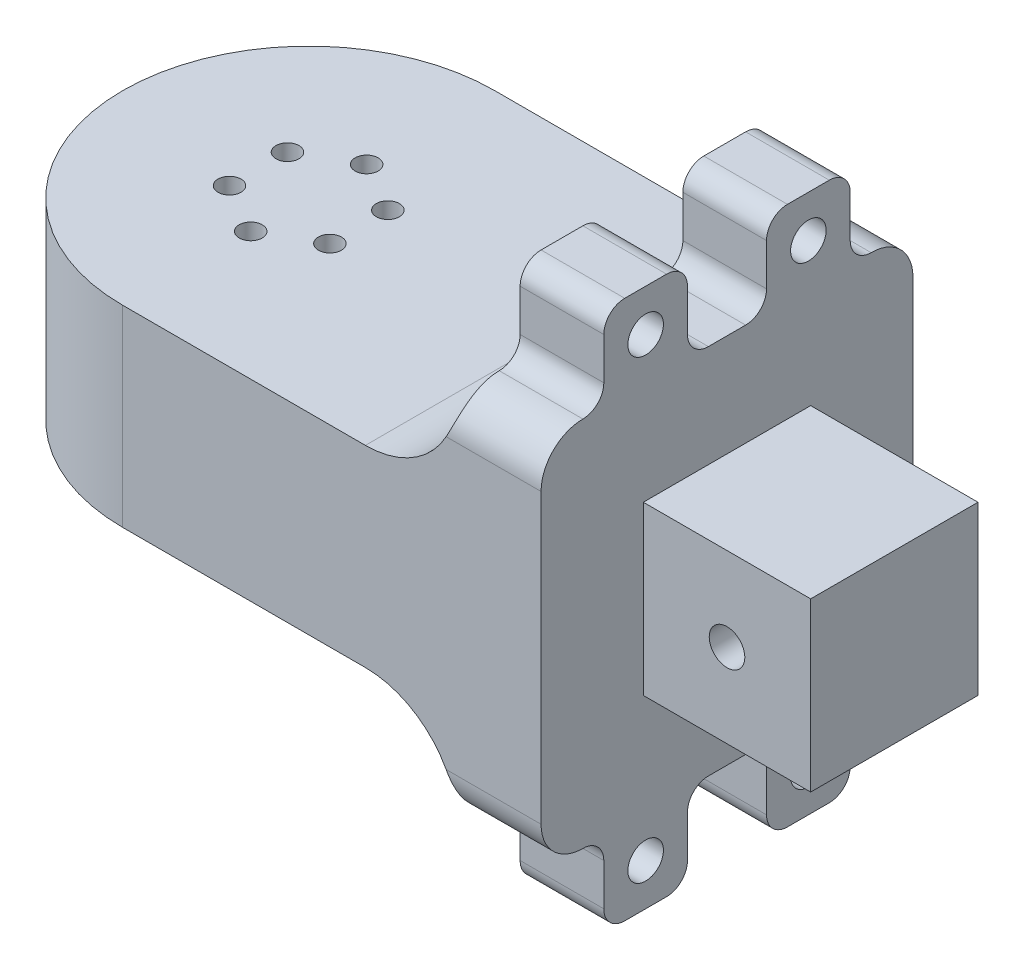
SolidWorks part; units mm, degrees
ref_plane "Front Plane" through (0, 0, 0) normal (0, 0, 1) x (1, 0, 0)
ref_plane "Top Plane" through (0, 0, 0) normal (0, 1, 0) x (1, 0, 0)
ref_plane "Right Plane" through (0, 0, 0) normal (1, 0, 0) x (0, 0, -1)
sketch "Sketch1" plane through (0, 0, 0) normal (0, 1, 0) x (1, 0, 0)
  line L0 (0, 44.45) -> (80, 44.45)
  line L1 (80, 44.45) -> (80, -44.45)
  line L2 (80, -44.45) -> (0, -44.45)
  arc A0 (0, 44.45) -> (0, -44.45) centre (0, 0) ccw
  dimension "D1" = 44.45
  dimension "D2" = 80
extrude "Boss-Extrude1" add sketch "Sketch1" along normal blind 46
sketch "Sketch2" plane through (0, 0, 0) normal (0, -1, 0) x (-1, 0, 0)
  line L1 (0, -13.8564) -> (12, -6.9282)
  line L2 (12, -6.9282) -> (12, 6.9282)
  line L3 (12, 6.9282) -> (0, 13.8564)
  line L4 (0, 13.8564) -> (-12, 6.9282)
  line L5 (-12, 6.9282) -> (-12, -6.9282)
  line L6 (-12, -6.9282) -> (0, -13.8564)
  circle A0 centre (0, 0) radius 12 construction
  circle A1 centre (0, -13.8564) radius 2.75
  circle A2 centre (12, -6.9282) radius 2.75
  circle A3 centre (12, 6.9282) radius 2.75
  circle A4 centre (0, 13.8564) radius 2.75
  circle A5 centre (-12, 6.9282) radius 2.75
  circle A6 centre (-12, -6.9282) radius 2.75
extrude "Cut-Extrude2" cut sketch "Sketch2" against normal blind 76 contours L6 A1 L1 | L5 A6 L6 | L4 A5 L5 | L3 A4 L4 | L2 A3 L3 | L1 A2 L2 | L2 A2 L1 | L1 A1 L6 | L6 A6 L5 | L5 A5 L4 | L4 A4 L3 | L3 A3 L2 region at (0, 0, 12.3403) region at (0, 0, 14.6145) region at (-10.687, 0, 6.1701) region at (-12.6565, 0, 7.3072) region at (12.6565, 0, 7.3072) region at (10.687, 0, 6.1701) region at (-10.687, 0, -6.1701) region at (-12.6565, 0, -7.3072) region at (12.6565, 0, -7.3072) region at (10.687, 0, -6.1701) region at (0, 0, -12.3403) region at (0, 0, -14.6145)
sketch "Sketch3" plane through (80, 0, 0) normal (1, 0, 0) x (0, 0, -1)
  line L2 (-44.45, 67.45) -> (-44.45, -21.45)
  line L4 (-44.45, 67.45) -> (44.45, 67.45)
  line L5 (44.45, 67.45) -> (44.45, -21.45)
  line L6 (-44.45, -21.45) -> (44.45, -21.45)
  dimension "D1" = 88.9
  dimension "D2" = 88.9
extrude "Boss-Extrude2" add sketch "Sketch3" along normal blind 20
fillet "Fillet1" radius 22 2 edges at (80, 46, 0) (80, 0, 0)
sketch "Sketch5" plane through (100, 0, 0) normal (1, 0, 0) x (0, 0, -1)
  line L0 (0, 23) -> (0, 43)
  line L1 (0, 43) -> (-20, 43)
  line L2 (-20, 43) -> (-20, 3)
  line L3 (-20, 3) -> (20, 3)
  line L4 (20, 3) -> (20, 43)
  line L5 (20, 43) -> (0, 43)
  dimension "D1" = 20
extrude "Boss-Extrude3" add sketch "Sketch5" along normal blind 40 contours L4 L5 L1 L2 L3 region at (100, 42.4343, -10)
sketch "Sketch7" plane through (0, 67.45, 0) normal (0, 1, 0) x (1, 0, 0)
  line L0 (80, 44.45) -> (80, -44.45) construction
  line L1 (80, 29.45) -> (100, 29.45)
  line L2 (80, 29.45) -> (80, 9.45)
  line L3 (80, 9.45) -> (100, 9.45)
  line L4 (100, 29.45) -> (100, 9.45)
  line L5 (100, 20) -> (100, -20) construction
  line L6 (100, 44.45) -> (80, 44.45) construction
  line L7 (100, 44.45) -> (100, -44.45) construction
  line L8 (80, -9.45) -> (100, -9.45)
  line L9 (80, -9.45) -> (80, -29.45)
  line L10 (80, -29.45) -> (100, -29.45)
  line L11 (100, -9.45) -> (100, -29.45)
  line L12 (100, -44.45) -> (80, -44.45) construction
  dimension "D1" = 20
  dimension "D2" = 15
  dimension "D3" = 20
  dimension "D4" = 15
extrude "Boss-Extrude4" add sketch "Sketch7" along normal blind 20
sketch "Sketch8" plane through (0, -21.45, 0) normal (0, -1, 0) x (1, 0, 0)
  line L0 (80, 44.45) -> (80, -44.45) construction
  line L1 (80, 29.45) -> (100, 29.45)
  line L2 (80, 29.45) -> (80, 9.45)
  line L3 (80, 9.45) -> (100, 9.45)
  line L4 (100, 29.45) -> (100, 9.45)
  line L5 (100, 44.45) -> (100, -44.45) construction
  line L6 (100, 44.45) -> (80, 44.45) construction
  line L7 (100, 20) -> (100, -20) construction
  line L8 (80, -29.45) -> (100, -29.45)
  line L9 (80, -29.45) -> (80, -9.45)
  line L10 (80, -9.45) -> (100, -9.45)
  line L11 (100, -29.45) -> (100, -9.45)
  line L12 (100, -44.45) -> (80, -44.45) construction
  dimension "D1" = 20
  dimension "D2" = 15
  dimension "D3" = 20
  dimension "D4" = 15
extrude "Boss-Extrude5" add sketch "Sketch8" along normal blind 20
fillet "Fillet2" radius 5 16 edges at (90, -41.45, -29.45) (90, -41.45, 29.45) (90, 87.45, -9.45) (90, 87.45, -29.45) (90, 87.45, 9.45) (90, 87.45, 29.45) (90, -41.45, -9.45) (90, -41.45, 9.45) (90, -21.45, -29.45) (90, -21.45, -9.45) (90, -21.45, 9.45) (90, -21.45, 29.45) (90, 67.45, 29.45) (90, 67.45, -29.45) (90, 67.45, -9.45) (90, 67.45, 9.45)
fillet "Fillet3" radius 10 4 edges at (90, -21.45, -44.45) (90, 67.45, -44.45) (90, 67.45, 44.45) (90, -21.45, 44.45)
sketch "Sketch10" plane through (80, 0, 0) normal (-1, 0, 0) x (0, 0, 1)
  line L0 (-24.45, 87.45) -> (-14.45, 87.45) construction
  line L1 (-9.45, 82.45) -> (-9.45, 72.45) construction
  line L2 (9.45, 82.45) -> (9.45, 72.45) construction
  line L3 (14.45, 87.45) -> (24.45, 87.45) construction
  line L4 (29.45, -36.45) -> (29.45, -26.45) construction
  line L5 (24.45, -41.45) -> (14.45, -41.45) construction
  line L6 (-14.45, -41.45) -> (-24.45, -41.45) construction
  line L7 (-29.45, -36.45) -> (-29.45, -26.45) construction
  circle A0 centre (-19.45, 77.45) radius 4.25
  circle A1 centre (19.45, 77.45) radius 4.25
  circle A2 centre (19.45, -31.45) radius 4.25
  circle A3 centre (-19.45, -31.45) radius 4.25
  dimension "D1" = 10
  dimension "D2" = 10
  dimension "D3" = 10
  dimension "D4" = 10
  dimension "D5" = 10
  dimension "D6" = 10
  dimension "D7" = 10
  dimension "D8" = 10
extrude "Cut-Extrude4" cut sketch "Sketch10" against normal blind 20
sketch "Sketch11" plane through (0, 0, -20) normal (0, 0, -1) x (-1, 0, 0)
  line L0 (-140, 3) -> (-140, 43) construction
  line L1 (-140, 43) -> (-100, 43) construction
  circle A0 centre (-120, 23) radius 4.25
  dimension "D1" = 20
  dimension "D2" = 20
extrude "Cut-Extrude5" cut sketch "Sketch11" against normal blind 102
